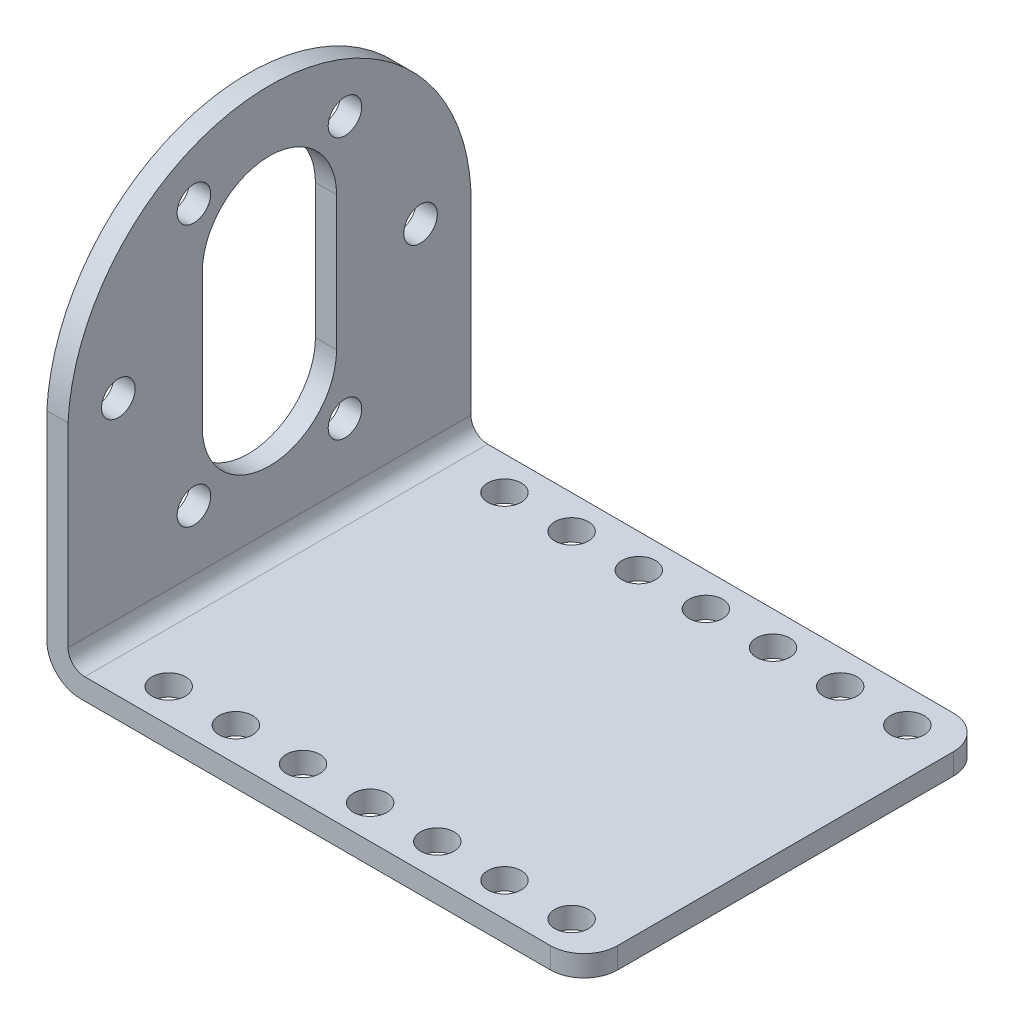
SolidWorks part; units mm, degrees
ref_plane "Front" through (0, 0, 0) normal (0, 0, 1) x (1, 0, 0)
ref_plane "Top" through (0, 0, 0) normal (0, 1, 0) x (1, 0, 0)
ref_plane "Right" through (0, 0, 0) normal (1, 0, 0) x (0, 0, -1)
sketch "Sketch1" plane through (0, 0, 0) normal (0, 1, 0) x (1, 0, 0)
  line L0 (-25.4, 19.05) -> (-25.4, -19.05)
  line L1 (-25.4, 19.05) -> (25.4, 19.05)
  line L3 (-25.4, -19.05) -> (25.4, -19.05)
  line L4 (25.4, 19.05) -> (25.4, -19.05)
  line L5 (-25.4, 19.05) -> (25.4, -19.05) construction
  line L6 (-25.4, -19.05) -> (25.4, 19.05) construction
  point P3 (0, 0)
  dimension "D1" = 50.8
  dimension "D2" = 38.1
extrude "Boss-Extrude1" add sketch "Sketch1" along normal blind 2
sketch "Sketch2" plane through (0, 2, 0) normal (0, 1, 0) x (1, 0, 0)
  line L0 (-25.4, -19.05) -> (25.4, -19.05) construction
  line L1 (-25.4, 19.05) -> (-23.4, 19.05)
  line L2 (-25.4, 19.05) -> (-25.4, -19.05)
  line L3 (-25.4, -19.05) -> (-23.4, -19.05)
  line L4 (-23.4, 19.05) -> (-23.4, -19.05)
  dimension "D1" = 2
extrude "Boss-Extrude2" add sketch "Sketch2" along normal blind 38.1
sketch "Sketch3" plane through (-25.4, 0, 0) normal (-1, 0, 0) x (0, 0, 1)
  line L0 (-19.05, 20.05) -> (19.05, 20.05) construction
  line L1 (-19.05, 40.1) -> (-19.05, 0) construction
  line L2 (19.05, 40.1) -> (19.05, 0) construction
  line L3 (-19.05, 40.1) -> (19.05, 40.1) construction
  line L4 (-19.05, 20.05) -> (-19.05, 40.1)
  line L5 (-19.05, 40.1) -> (19.05, 40.1)
  line L6 (19.05, 40.1) -> (19.05, 20.05)
  arc A0 (-19.05, 20.05) -> (19.05, 20.05) centre (0, 21.0251) cw
  line M4 (19.05, 40.1) -> (-19.05, 40.1)
  line M5 (-19.05, 40.1) -> (-19.05, 0)
extrude "Cut-Extrude2" cut sketch "Sketch3" against normal blind 38.1 contours A0 L6 M4 | A0 L5 M5 region at (-25.4, 35.8686, 14.7891) region at (-25.4, 35.8686, -14.7891)
sketch "Sketch4" plane through (0, 2, 0) normal (0, 1, 0) x (1, 0, 0)
  line L0 (-23.4, 15.875) -> (25.4, 15.875) construction
  line L1 (25.4, -19.05) -> (25.4, 19.05) construction
  line L2 (-23.4, -19.05) -> (-23.4, 19.05) construction
  line L4 (25.4, 19.05) -> (-23.4, 19.05) construction
  circle A0 centre (-17.05, 15.875) radius 1.5875
  dimension "D2" = 3.175
  dimension "D1" = 3.175
  dimension "D3" = 6.35
extrude "Cut-Extrude3" cut sketch "Sketch4" against normal up to surface (2 mm away) up to face at (0, 0, 0)
pattern_linear "LPattern1" count 7 spacing 6.35 along (1, 0, 0) of "Cut-Extrude3"
mirror "Mirror1" about plane through (0, 0, 0) normal (0, 0, 1) of "LPattern1", "Cut-Extrude3"
fillet "Fillet1" radius 3.175 2 edges at (25.4, 1, -19.05) (25.4, 1, 19.05)
fillet "Fillet2" radius 1.5875 1 edges at (-23.4, 2, 0)
fillet "Fillet3" radius 3.175 1 edges at (-25.4, 0, 0)
sketch "Sketch5" plane through (-25.4, 0, 0) normal (-1, 0, 0) x (0, 0, 1)
  line L0 (0, 40.1) -> (0, 27.9875) construction
  line L1 (-19.05, 3.175) -> (19.05, 3.175) construction
  line L2 (-6.35, 15.2875) -> (6.35, 15.2875) construction
  line L3 (6.35, 27.9875) -> (-6.35, 27.9875) construction
  line L4 (-6.35, 27.9875) -> (-6.35, 15.2875)
  line L5 (6.35, 27.9875) -> (6.35, 15.2875)
  line L6 (28.399, 8.9952) -> (77.199, 8.9952) construction
  line L7 (28.399, 8.9952) -> (77.199, 8.9952) construction
  line L8 (0, 21.6375) -> (14.2875, 21.6375) construction
  line L10 (0, 15.2875) -> (0, 3.175) construction
  line L11 (0, 27.9875) -> (0, 15.2875) construction
  arc A0 (19.05, 22.0001) -> (-19.05, 22.0001) centre (0, 21.0251) ccw construction
  arc A1 (6.35, 27.9875) -> (-6.35, 27.9875) centre (0, 27.9875) ccw
  arc A2 (-6.35, 15.2875) -> (6.35, 15.2875) centre (0, 15.2875) ccw
  circle A3 centre (14.2875, 21.6375) radius 1.5875
  circle A9 centre (7.1437, 9.2642) radius 1.5875
  circle A10 centre (-7.1438, 9.2642) radius 1.5875
  circle A11 centre (-14.2875, 21.6375) radius 1.5875
  circle A12 centre (-7.1437, 34.0108) radius 1.5875
  circle A13 centre (7.1438, 34.0108) radius 1.5875
  point P19 (0, 34.3375)
  point P33 (0, 21.6375)
  dimension "D1" = 12.7
  dimension "D4" = 3.175
  dimension "D2" = 12.7
  dimension "D5" = 14.2875
extrude "Cut-Extrude4" cut sketch "Sketch5" against normal through all contours A13 | L4 A2 L5 A1 | A12 | A3 | A11 | A10 | A9 region at (-25.4, 21.6375, 0) region at (-25.4, 21.6375, 14.2875) region at (-25.4, 9.2642, 7.1437) region at (-25.4, 9.2642, -7.1438) region at (-25.4, 21.6375, -14.2875) region at (-25.4, 34.0108, -7.1437) region at (-25.4, 34.0108, 7.1438)
